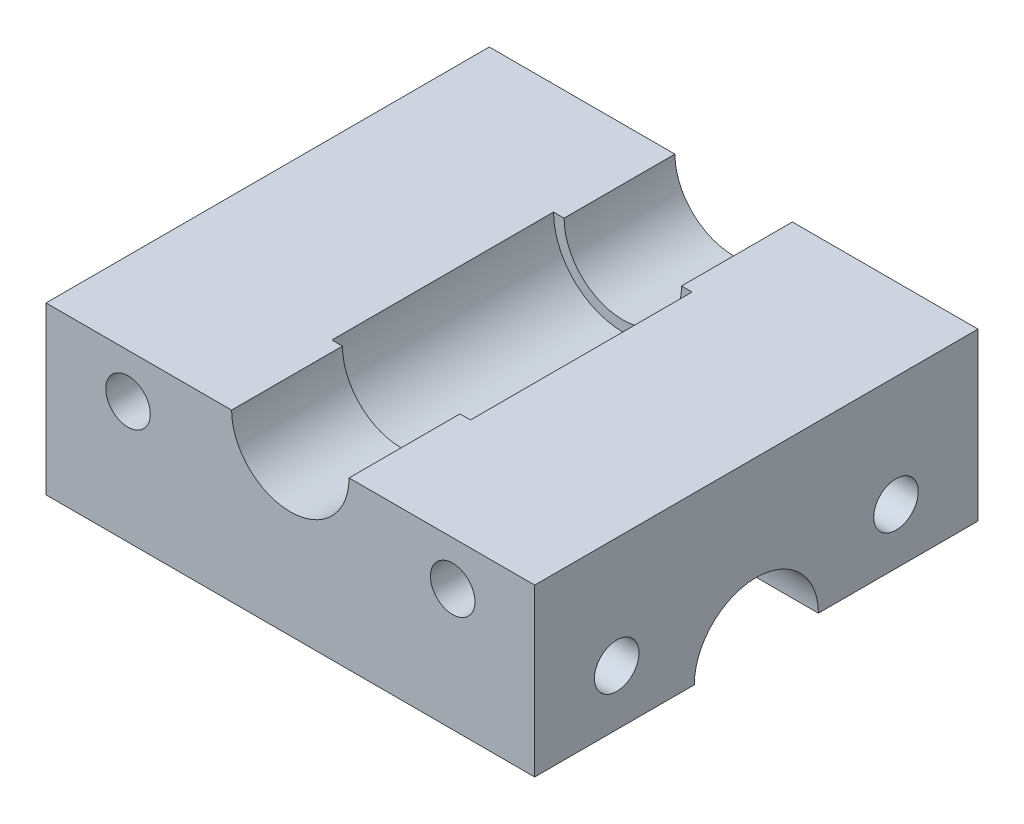
SolidWorks part; units mm, degrees
ref_plane "Front Plane" through (0, 0, 0) normal (0, 0, 1) x (1, 0, 0)
ref_plane "Top Plane" through (0, 0, 0) normal (0, 1, 0) x (1, 0, 0)
ref_plane "Right Plane" through (0, 0, 0) normal (1, 0, 0) x (0, 0, -1)
sketch "Sketch1" plane through (0, 0, 0) normal (0, 0, 1) x (1, 0, 0)
  line L0 (23.737, 16.5733) -> (45.006, 16.5733)
  line L1 (-10.994, -2.4767) -> (45.006, -2.4767)
  line L2 (-10.994, -2.4767) -> (-10.994, 16.5733)
  line L3 (-10.994, 16.5733) -> (10.275, 16.5733)
  line L4 (45.006, -2.4767) -> (45.006, 16.5733)
  line L5 (17.006, -2.4767) -> (17.006, 54.6755) construction
  arc A0 (23.737, 16.5733) -> (10.275, 16.5733) centre (17.006, 16.5733) cw
  dimension "D3" = 6.731
  dimension "D1" = 19.05
  dimension "D2" = 56
extrude "Boss-Extrude1" add sketch "Sketch1" along normal blind 50.8
ref_plane "Plane1" through (0, 0, 25.4) normal (0, 0, 1) x (1, 0, 0)
sketch "Sketch2" plane through (0, 0, 25.4) normal (0, 0, 1) x (1, 0, 0)
  circle A0 centre (17.006, 16.5733) radius 7.9375
  dimension "D1" = 15.875
extrude "Cut-Extrude1" cut sketch "Sketch2" against normal mid plane 25.4
hole_wizard "#10 Clearance Hole1" positions "3DSketch1" profile "Sketch5" hole size "#10" standard "ANSI Inch" end condition through all
sketch3d "3DSketch1"
  line L0 (-10.994, -2.4767, 50.8) -> (-10.994, -2.4767, 0) construction
  line L1 (-10.994, 16.5733, 50.8) -> (-10.994, -2.4767, 50.8) construction
  line L2 (-10.994, 16.5733, 0) -> (-10.994, -2.4767, 0) construction
  line L3 (45.006, -2.4767, 50.8) -> (45.006, 16.5733, 50.8) construction
  line L4 (-10.994, -2.4767, 50.8) -> (45.006, -2.4767, 50.8) construction
  point P0 (-10.994, 3.8733, 41.402)
  point P4 (-1.596, 11.4933, 50.8)
  point P6 (35.608, 11.4933, 50.8)
  point P20 (-10.994, 3.8733, 9.398)
  dimension "D1" = 6.35
  dimension "D2" = 9.398
  dimension "D3" = 9.398
  dimension "D4" = 9.398
  dimension "D5" = 9.398
  dimension "D6" = 13.97
sketch "Sketch5" plane through (-10.994, 3.8733, 41.402) normal (0, 1, 0) x (0, 0, 1)
  line L0 (0, 0) -> (0, 56)
  line L1 (0, 56) -> (2.5527, 56)
  line L2 (2.5527, 56) -> (2.5527, 0)
  line L5 (2.5527, 0) -> (0, 0)
  line L11 (0, -6.35) -> (0, 107.95) construction
  dimension "Thru Hole Dia." = 5.1054
  dimension "Thru Hole Depth" = 56
sketch "Sketch9" plane through (45.006, 0, 0) normal (1, 0, 0) x (0, 0, -1)
  line L0 (-50.8, -2.4767) -> (0, -2.4767) construction
  line L1 (-32.512, -2.4767) -> (-18.288, -2.4767)
  arc A0 (-18.288, -2.4767) -> (-32.512, -2.4767) centre (-25.4, -2.4767) ccw
  circle A1 centre (-9.398, 3.8733) radius 2.5527 construction
  dimension "D1" = 8.89
extrude "Cut-Extrude4" cut sketch "Sketch9" against normal through all contours A0 L1
equation "\"D2@3DSketch1\"=\"D3@3DSketch1\""
equation "\"D4@3DSketch1\"=\"D3@3DSketch1\""
equation "\"D5@3DSketch1\"=\"D3@3DSketch1\""
